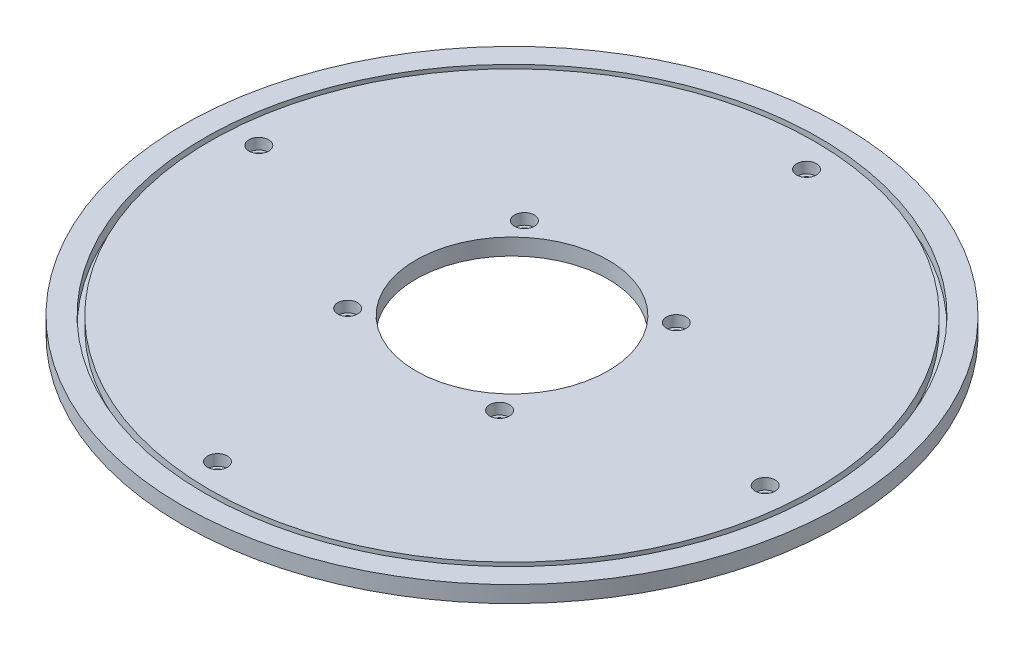
SolidWorks part; units mm, degrees
ref_plane "Front Plane" through (0, 0, 0) normal (0, 0, 1) x (1, 0, 0)
ref_plane "Top Plane" through (0, 0, 0) normal (0, 1, 0) x (1, 0, 0)
ref_plane "Right Plane" through (0, 0, 0) normal (1, 0, 0) x (0, 0, -1)
sketch "Sketch1" plane through (0, 0, 0) normal (0, 1, 0) x (1, 0, 0)
  circle A0 centre (0, 0) radius 300
  point P0 (0, 0)
  dimension "D1" = 600
extrude "plate" add sketch "Sketch1" along normal blind 15
sketch "Sketch2" plane through (0, 15, 0) normal (0, 1, 0) x (1, 0, 0)
  circle A0 centre (0, 0) radius 87.5
  dimension "D1" = 175
extrude "bearing-hole" cut sketch "Sketch2" against normal through all
sketch "Sketch4" plane through (0, 15, 0) normal (0, 1, 0) x (1, 0, 0)
  circle A0 centre (0, 0) radius 280
  circle A1 centre (0, 0) radius 275
  point P0 (0, 0)
  point P6 (0, 0)
  dimension "D1" = 560
  dimension "D2" = 550
extrude "Cut-Extrude3" cut sketch "Sketch4" against normal blind 10
hole_wizard "CBORE for M10 SHCS" positions "Sketch5" profile "Sketch6" counterbore size "M10" standard "ANSI Metric" end condition through all
sketch "Sketch5" plane through (0, 15, 0) normal (0, 1, 0) x (0.9972, 0, 0.0753)
  line L1 (75, -75) -> (-75, -75) construction
  line L2 (75, -75) -> (75, 75) construction
  line L3 (75, 75) -> (-75, 75) construction
  line L4 (-75, -75) -> (-75, 75) construction
  line L5 (75, -75) -> (-75, 75) construction
  line L6 (75, 75) -> (-75, -75) construction
  line L7 (-250, 0) -> (0, 250) construction
  line L8 (-250, 0) -> (0, -250) construction
  line L9 (0, 250) -> (250, 0) construction
  line L10 (0, -250) -> (250, 0) construction
  line L11 (-250, 0) -> (250, 0) construction
  line L12 (0, 250) -> (0, -250) construction
  point P36 (0, 0)
  point P198 (-75, 75)
  point P201 (75, 75)
  point P204 (75, -75)
  point P207 (-75, -75)
  point P210 (0, 0)
  point P341 (0, 250)
  point P344 (-250, 0)
  point P347 (250, 0)
  point P350 (0, -250)
sketch "Sketch6" plane through (0, 15, 0) normal (1, 0, 0) x (0, 0, 1)
  line L0 (0, 0) -> (0, 15)
  line L1 (0, 15) -> (6, 15)
  line L2 (6, 15) -> (6, 10)
  line L3 (6, 10) -> (9, 10)
  line L4 (9, 10) -> (9, 0)
  line L5 (9, 0) -> (0, 0)
  line L6 (0, -6.35) -> (0, 107.95) construction
  dimension "Thru Hole Dia." = 12
  dimension "Thru Hole Depth" = 15
  dimension "C'Bore Dia." = 18
  dimension "C'Bore Depth" = 10
